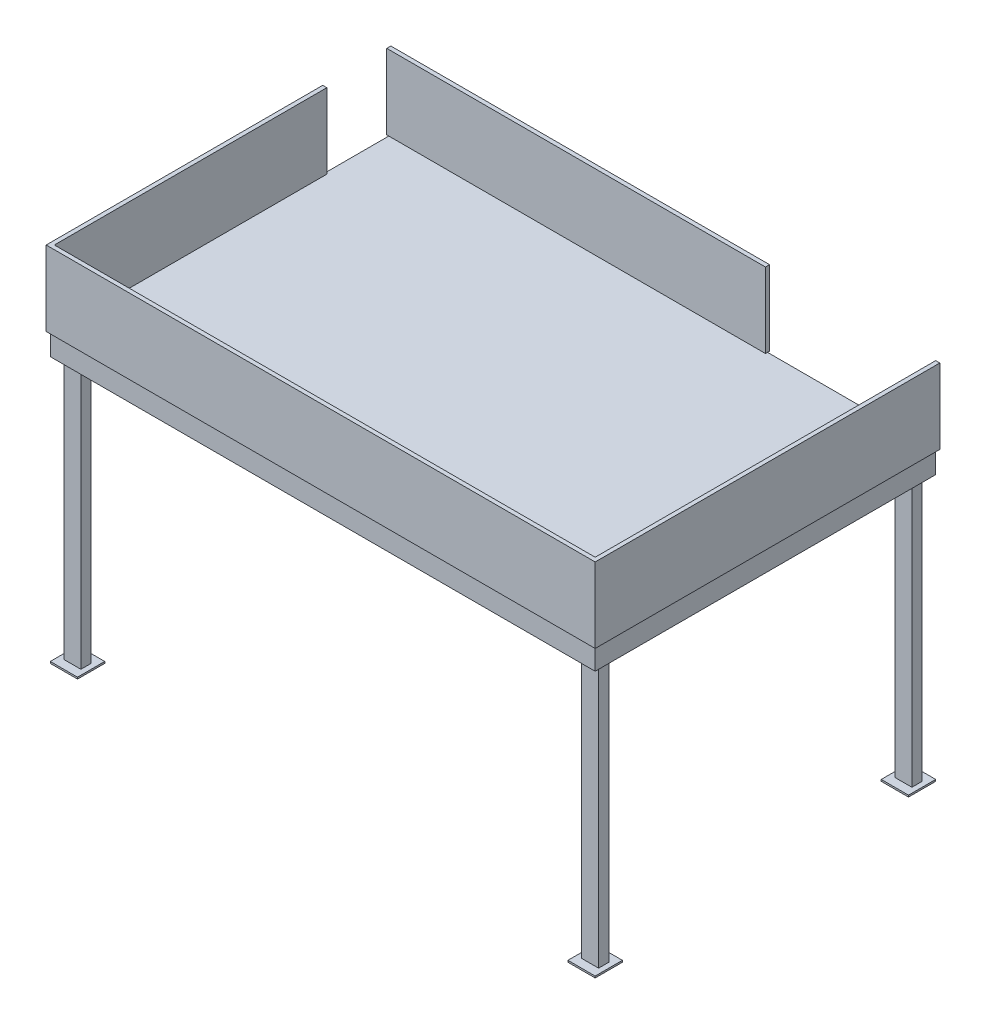
SolidWorks part; units mm, degrees
ref_plane "Front Plane" through (0, 0, 0) normal (0, 0, 1) x (1, 0, 0)
ref_plane "Top Plane" through (0, 0, 0) normal (0, 1, 0) x (1, 0, 0)
ref_plane "Right Plane" through (0, 0, 0) normal (1, 0, 0) x (0, 0, -1)
other "Configuration Table"
sketch "Sketch1" plane through (0, 0, 0) normal (0, 1, 0) x (1, 0, 0)
  line L1 (-4000, -2500) -> (-3600, -2500)
  line L2 (-4000, -2500) -> (-4000, -2100)
  line L3 (-4000, -2100) -> (-3600, -2100)
  line L4 (-3600, -2500) -> (-3600, -2100)
extrude "Boss-Extrude1" add sketch "Sketch1" along normal blind 25
sketch "Sketch2" plane through (0, 0, 0) normal (0, 1, 0) x (1, 0, 0)
  line L1 (-4000, 2100) -> (-3600, 2100)
  line L2 (-4000, 2100) -> (-4000, 2500)
  line L3 (-4000, 2500) -> (-3600, 2500)
  line L4 (-3600, 2100) -> (-3600, 2500)
extrude "Boss-Extrude2" add sketch "Sketch2" along normal blind 25
sketch "Sketch3" plane through (0, 0, 0) normal (0, 1, 0) x (1, 0, 0)
  line L1 (3600, -2500) -> (4000, -2500)
  line L2 (3600, -2500) -> (3600, -2100)
  line L3 (3600, -2100) -> (4000, -2100)
  line L4 (4000, -2500) -> (4000, -2100)
extrude "Boss-Extrude3" add sketch "Sketch3" along normal blind 25
sketch "Sketch4" plane through (0, 0, 0) normal (0, 1, 0) x (1, 0, 0)
  line L1 (3600, 2100) -> (4000, 2100)
  line L2 (3600, 2100) -> (3600, 2500)
  line L3 (3600, 2500) -> (4000, 2500)
  line L4 (4000, 2100) -> (4000, 2500)
extrude "Boss-Extrude4" add sketch "Sketch4" along normal blind 25
sketch "Sketch5" plane through (0, 0, 0) normal (0, 1, 0) x (1, 0, 0)
  line L1 (-3925, -2375) -> (-3675, -2375)
  line L2 (-3925, -2375) -> (-3925, -2225)
  line L3 (-3925, -2225) -> (-3675, -2225)
  line L4 (-3675, -2375) -> (-3675, -2225)
extrude "Boss-Extrude5" add sketch "Sketch5" along normal blind 4175 from offset 25
sketch "Sketch6" plane through (0, 0, 0) normal (0, 1, 0) x (1, 0, 0)
  line L1 (-3925, 2225) -> (-3675, 2225)
  line L2 (-3925, 2225) -> (-3925, 2375)
  line L3 (-3925, 2375) -> (-3675, 2375)
  line L4 (-3675, 2225) -> (-3675, 2375)
extrude "Boss-Extrude6" add sketch "Sketch6" along normal blind 4175 from offset 25
sketch "Sketch7" plane through (0, 0, 0) normal (0, 1, 0) x (1, 0, 0)
  line L1 (3675, -2375) -> (3925, -2375)
  line L2 (3675, -2375) -> (3675, -2225)
  line L3 (3675, -2225) -> (3925, -2225)
  line L4 (3925, -2375) -> (3925, -2225)
extrude "Boss-Extrude7" add sketch "Sketch7" along normal blind 4175 from offset 25
sketch "Sketch8" plane through (0, 0, 0) normal (0, 1, 0) x (1, 0, 0)
  line L1 (3675, 2225) -> (3925, 2225)
  line L2 (3675, 2225) -> (3675, 2375)
  line L3 (3675, 2375) -> (3925, 2375)
  line L4 (3925, 2225) -> (3925, 2375)
extrude "Boss-Extrude8" add sketch "Sketch8" along normal blind 4175 from offset 25
sketch "Sketch9" plane through (0, 0, 0) normal (0, 1, 0) x (1, 0, 0)
  line L1 (-4000, -2500) -> (4000, -2500)
  line L2 (-4000, -2500) -> (-4000, 2500)
  line L3 (-4000, 2500) -> (4000, 2500)
  line L4 (4000, -2500) -> (4000, 2500)
extrude "Boss-Extrude9" add sketch "Sketch9" along normal blind 300 from offset 3900
sketch "Sketch10" plane through (0, 0, 0) normal (0, 1, 0) x (1, 0, 0)
  line L1 (-4000, -2500) -> (4000, -2500)
  line L2 (-4000, -2500) -> (-4000, 2500)
  line L3 (-4000, 2500) -> (4000, 2500)
  line L4 (4000, -2500) -> (4000, 2500)
extrude "Boss-Extrude10" add sketch "Sketch10" along normal blind 20 from offset 4200
sketch "Sketch11" plane through (0, 0, 0) normal (0, 1, 0) x (1, 0, 0)
  line L1 (-4030, -2530) -> (4030, -2530)
  line L2 (-4030, -2530) -> (-4030, -2470)
  line L3 (-4030, -2470) -> (4030, -2470)
  line L4 (4030, -2530) -> (4030, -2470)
extrude "Boss-Extrude11" add sketch "Sketch11" along normal blind 1100 from offset 4220
sketch "Sketch12" plane through (0, 0, 0) normal (0, 1, 0) x (1, 0, 0)
  line L0 (-4030, -2530) -> (4030, -2530) construction
  line L1 (3970, -2530) -> (4030, -2530)
  line L2 (3970, -2530) -> (3970, 2530)
  line L3 (3970, 2530) -> (4030, 2530)
  line L4 (4030, -2530) -> (4030, 2530)
extrude "Boss-Extrude12" add sketch "Sketch12" along normal blind 1100 from offset 4220
sketch "Sketch13" plane through (0, 0, 0) normal (0, 1, 0) x (1, 0, 0)
  line L1 (-4030, 2470) -> (1530, 2470)
  line L2 (-4030, 2470) -> (-4030, 2530)
  line L3 (-4030, 2530) -> (1530, 2530)
  line L4 (1530, 2470) -> (1530, 2530)
extrude "Boss-Extrude13" add sketch "Sketch13" along normal blind 1100 from offset 4220
sketch "Sketch14" plane through (0, 0, 0) normal (0, 1, 0) x (1, 0, 0)
  line L1 (-4030, -2530) -> (-3970, -2530)
  line L2 (-4030, -2530) -> (-4030, 1530)
  line L3 (-4030, 1530) -> (-3970, 1530)
  line L4 (-3970, -2530) -> (-3970, 1530)
extrude "Boss-Extrude14" add sketch "Sketch14" along normal blind 1100 from offset 4220
sketch "Sketch15" plane through (0, 0, 0) normal (0, 1, 0) x (1, 0, 0)
  line L1 (-4900, 1500) -> (-4000, 1500)
  line L2 (-4900, 1500) -> (-4900, 4500)
  line L3 (-4900, 4500) -> (-4000, 4500)
  line L4 (-4000, 1500) -> (-4000, 4500)
extrude "Boss-Extrude15" add sketch "Sketch15" along normal blind 2100 draft 35
